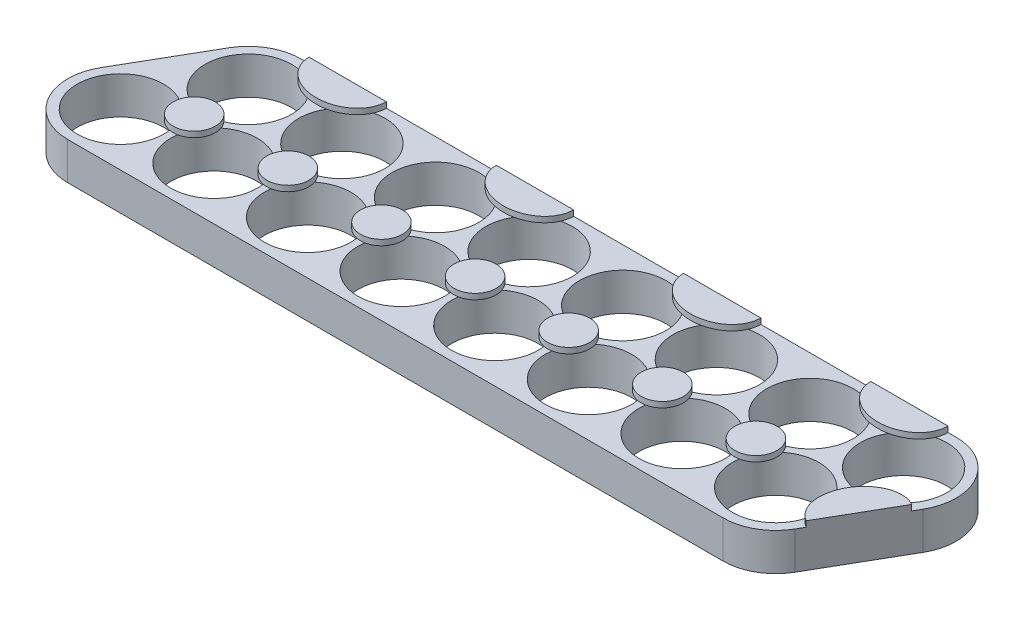
SolidWorks part; units mm, degrees
ref_plane "Front Plane" through (0, 0, 0) normal (0, 0, 1) x (1, 0, 0)
ref_plane "Top Plane" through (0, 0, 0) normal (0, 1, 0) x (1, 0, 0)
ref_plane "Right Plane" through (0, 0, 0) normal (1, 0, 0) x (0, 0, -1)
sketch "Sketch2" plane through (0, 0, 0) normal (0, 1, 0) x (1, 0, 0)
  line L0 (10, 17.3205) -> (0, 0) construction
  line L1 (0, 0) -> (20, 0) construction
  line L2 (20, 0) -> (10, 17.3205) construction
  line L3 (0.2572, 22.9455) -> (-9.7428, 5.625)
  line L4 (0, -11.25) -> (140, -11.25)
  line L5 (20, 0) -> (40, 0) construction
  line L6 (10, 17.3205) -> (30, 17.3205) construction
  line L7 (50, 17.3205) -> (30, 17.3205) construction
  line L8 (10, 28.5705) -> (150, 28.5705)
  line L9 (159.7428, 11.6955) -> (149.7428, -5.625)
  circle A0 centre (10, 17.3205) radius 9.25
  circle A1 centre (0, 0) radius 9.25
  circle A2 centre (20, 0) radius 9.25
  arc A5 (-9.7428, 5.625) -> (0, -11.25) centre (0, 0) ccw
  arc A6 (140, -11.25) -> (149.7428, -5.625) centre (140, 0) ccw
  circle A10 centre (40, 0) radius 9.25
  circle A11 centre (60, 0) radius 9.25
  circle A12 centre (80, 0) radius 9.25
  circle A13 centre (100, 0) radius 9.25
  circle A14 centre (120, 0) radius 9.25
  circle A15 centre (140, 0) radius 9.25
  circle A16 centre (30, 17.3205) radius 9.25
  circle A17 centre (50, 17.3205) radius 9.25
  circle A18 centre (70, 17.3205) radius 9.25
  circle A19 centre (90, 17.3205) radius 9.25
  circle A20 centre (110, 17.3205) radius 9.25
  circle A21 centre (130, 17.3205) radius 9.25
  circle A22 centre (150, 17.3205) radius 9.25
  arc A23 (159.7428, 11.6955) -> (150, 28.5705) centre (150, 17.3205) ccw
  arc A25 (10, 28.5705) -> (0.2572, 22.9455) centre (10, 17.3205) ccw
  point P7 (10, 0)
  dimension "D1" = 18.5
  dimension "D2" = 1.5
  dimension "D3" = 1.5
  dimension "D4" = 7
  dimension "D6" = 2
  dimension "D8" = 172.5
  dimension "D7" = 39.8205
  dimension "D9" = 20
  dimension "D5" = 7
extrude "Boss-Extrude1" add sketch "Sketch2" along normal mid plane 8
sketch "Sketch3" plane through (0, 4, 0) normal (0, 1, 0) x (1, 0, 0)
  line L0 (10, 17.3205) -> (10, 5.7735) construction
  line L1 (10, 5.7735) -> (0, 0) construction
  line L2 (0, 0) -> (20, 0) construction
  line L3 (130, 17.3205) -> (130, 5.7735) construction
  line L4 (130, 5.7735) -> (140, 0) construction
  line L5 (10, 17.3205) -> (20, 11.547) construction
  line L6 (150, 28.5705) -> (10, 28.5705) construction
  line L7 (-3.4641, 2) -> (3.4641, -2) construction
  line L8 (0, 4) -> (20, 4) construction
  line L9 (0, 4) -> (0, -4) construction
  line L10 (0, -4) -> (20, -4) construction
  line L11 (20, 4) -> (20, -4) construction
  line L12 (-3.4641, 2) -> (6.5359, 19.3205) construction
  line L13 (3.4641, -2) -> (13.4641, 15.3205) construction
  line L14 (6.5359, 19.3205) -> (13.4641, 15.3205) construction
  line L15 (13.4641, 19.3205) -> (6.5359, 15.3205) construction
  line L16 (13.4641, 19.3205) -> (23.4641, 2) construction
  line L17 (6.5359, 15.3205) -> (16.5359, -2) construction
  line L18 (23.4641, 2) -> (16.5359, -2) construction
  line L19 (30, 13.3205) -> (10, 13.3205) construction
  line L20 (30, 13.3205) -> (30, 21.3205) construction
  line L21 (30, 21.3205) -> (10, 21.3205) construction
  line L22 (10, 13.3205) -> (10, 21.3205) construction
  line L23 (28.25, 28.5705) -> (11.75, 28.5705)
  line L30 (68.25, 28.5705) -> (51.75, 28.5705)
  line L31 (108.25, 28.5705) -> (91.75, 28.5705)
  line L32 (148.25, 28.5705) -> (131.75, 28.5705)
  line L36 (149.7428, -5.625) -> (159.7428, 11.6955) construction
  line L37 (158.8678, 10.18) -> (150.6178, -4.1095)
  line L38 (20, 28.5705) -> (20, 21.8205) construction
  line L39 (154.7428, 3.0353) -> (148.8971, 6.4103) construction
  line L40 (148.8971, 6.4103) -> (130, 17.3205) construction
  circle A0 centre (10, 5.7735) radius 4.5
  circle A4 centre (30, 5.7735) radius 4.5
  circle A5 centre (50, 5.7735) radius 4.5
  circle A6 centre (70, 5.7735) radius 4.5
  circle A7 centre (90, 5.7735) radius 4.5
  circle A8 centre (110, 5.7735) radius 4.5
  circle A9 centre (130, 5.7735) radius 4.5
  ellipse E0 centre (20, 28.5705) end of major axis (28.25, 28.5705) minor radius 6.75 (11.75, 28.5705) -> (28.25, 28.5705) ccw
  ellipse E1 centre (60, 28.5705) end of major axis (68.25, 28.5705) minor radius 6.75 (51.75, 28.5705) -> (68.25, 28.5705) ccw
  ellipse E2 centre (100, 28.5705) end of major axis (108.25, 28.5705) minor radius 6.75 (91.75, 28.5705) -> (108.25, 28.5705) ccw
  ellipse E3 centre (140, 28.5705) end of major axis (148.25, 28.5705) minor radius 6.75 (131.75, 28.5705) -> (148.25, 28.5705) ccw
  ellipse E4 centre (154.7428, 3.0353) end of major axis (158.8678, 10.18) minor radius 6.75 (158.8678, 10.18) -> (150.6178, -4.1095) ccw
  point P27 (10, 17.3205)
  point P46 (0, 0)
  point P49 (10, 17.3205)
  point P55 (10, 17.3205)
  point P58 (20, 0)
  dimension "D1" = 4
  dimension "D3" = 0.5
  dimension "D6" = 9
  dimension "D4" = 8
  dimension "D5" = 16.5
  dimension "D2" = 7
extrude "Boss-Extrude2" add sketch "Sketch3" along normal blind 1.2
mirror "Mirror1" [suppressed] of bodies 102
sketch "Sketch5" [suppressed] plane through (0, 0, 0) normal (0, 0, 1) x (1, 0, 0)
  line L0 (161.25, -4) -> (161.25, 4) construction
  line L1 (-11.25, -4) -> (161.25, -4)
  line L2 (-11.25, -4) -> (-11.25, 5.2)
  line L3 (-11.25, 5.2) -> (161.25, 5.2)
  line L4 (161.25, -4) -> (161.25, 5.2)
  line L5 (-11.25, -4) -> (161.25, 5.2) construction
  line L6 (-11.25, 5.2) -> (161.25, -4) construction
  line L7 (114.5, 5.2) -> (105.5, 5.2) construction
  point P4 (75, 0.6)
extrude "Cut-Extrude1" [suppressed] cut sketch "Sketch5" against normal through all both and the other way through all
